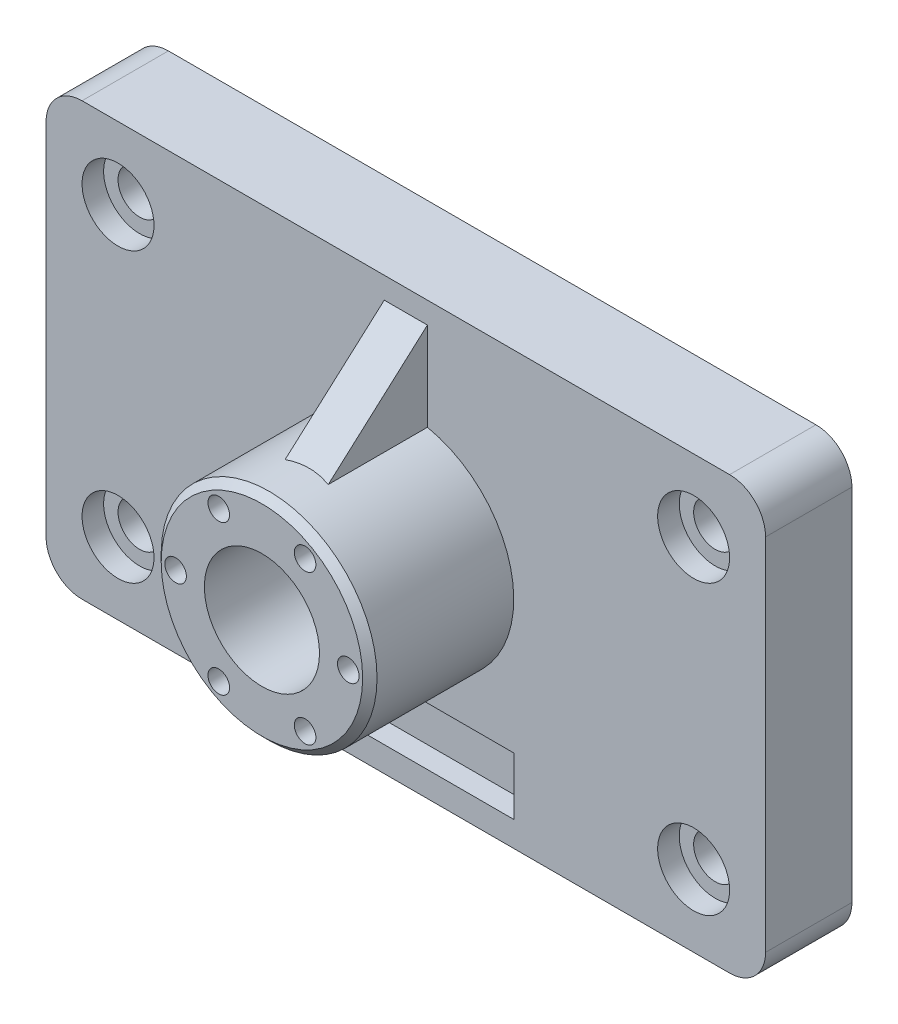
SolidWorks part; units mm, degrees
ref_plane "前视基准面" through (0, 0, 0) normal (0, 0, 1) x (1, 0, 0)
ref_plane "上视基准面" through (0, 0, 0) normal (0, 1, 0) x (1, 0, 0)
ref_plane "右视基准面" through (0, 0, 0) normal (1, 0, 0) x (0, 0, -1)
other "Configuration Table"
sketch "Sketch1" plane through (0, 0, 0) normal (0, 0, 1) x (1, 0, 0)
  line L1 (-50, -30) -> (50, -30)
  line L2 (-50, -30) -> (-50, 30)
  line L3 (-50, 30) -> (50, 30)
  line L4 (50, -30) -> (50, 30)
extrude "Boss-Extrude1" add sketch "Sketch1" along normal blind 12
fillet "Fillet1" radius 5 4 edges at (-50, 30, 6) (50, 30, 6) (50, -30, 6) (-50, -30, 6)
sketch "Sketch2" plane through (0, 0, 12) normal (0, 0, 1) x (1, 0, 0)
  circle A0 centre (0, 0) radius 15
extrude "Boss-Extrude2" add sketch "Sketch2" along normal blind 20
chamfer "Chamfer1" distance 1 angle 45 1 edges at (15, 0, 32) tangent propagation no
sketch "Sketch3" plane through (0, 0, 32) normal (0, 0, 1) x (1, 0, 0)
  circle A0 centre (0, 0) radius 8
extrude "Cut-Extrude2" cut sketch "Sketch3" against normal through all
sketch "Sketch4" plane through (0, 0, 12) normal (0, 0, 1) x (1, 0, 0)
  circle A0 centre (-40, -20) radius 5
  circle A1 centre (-40, 20) radius 5
  circle A2 centre (40, -20) radius 5
  circle A3 centre (40, 20) radius 5
extrude "Cut-Extrude4" cut sketch "Sketch4" against normal blind 3
sketch "Sketch5" plane through (0, 0, 12) normal (0, 0, 1) x (1, 0, 0)
  circle A0 centre (-40, -20) radius 3
  circle A1 centre (-40, 20) radius 3
  circle A2 centre (40, -20) radius 3
  circle A3 centre (40, 20) radius 3
extrude "Cut-Extrude6" cut sketch "Sketch5" against normal through all
sketch "Sketch6" plane through (0, 0, 12) normal (0, 0, 1) x (1, 0, 0)
  line L0 (-15, -26.5) -> (15, -26.5)
  line L1 (15, -26.5) -> (15, -18.5)
  line L2 (15, -18.5) -> (-15, -18.5)
  line L3 (-15, -18.5) -> (-15, -26.5)
extrude "Cut-Extrude8" cut sketch "Sketch6" against normal blind 3
sketch "Sketch7" plane through (0, 0, 32) normal (0, 0, 1) x (1, 0, 0)
  circle A0 centre (12, 0) radius 1.5
extrude "Cut-Extrude10" cut sketch "Sketch7" against normal blind 8
ref_axis "Axis1" through (0, 0, -1.6) along (0, 0, 1)
pattern_circular "CirPattern1" count 6 over 360 about axis through (0, 0, -1.6) along (0, 0, 1) of "Cut-Extrude10"
sketch "Sketch8" plane through (0, 0, 0) normal (1, 0, 0) x (0, 0, -1)
  line L0 (-12, 27) -> (-26, 14.5)
rib "Rib2" sketch "Sketch8<2>" sketch "Sketch8<2>" thickness 6 extrusion direction parallel to sketch draft on no parameters "D1"=6
sketch "Sketch8<2>" plane through (0, 0, 0) normal (1, 0, 0) x (0, 0, -1) same geometry as "Sketch8"
